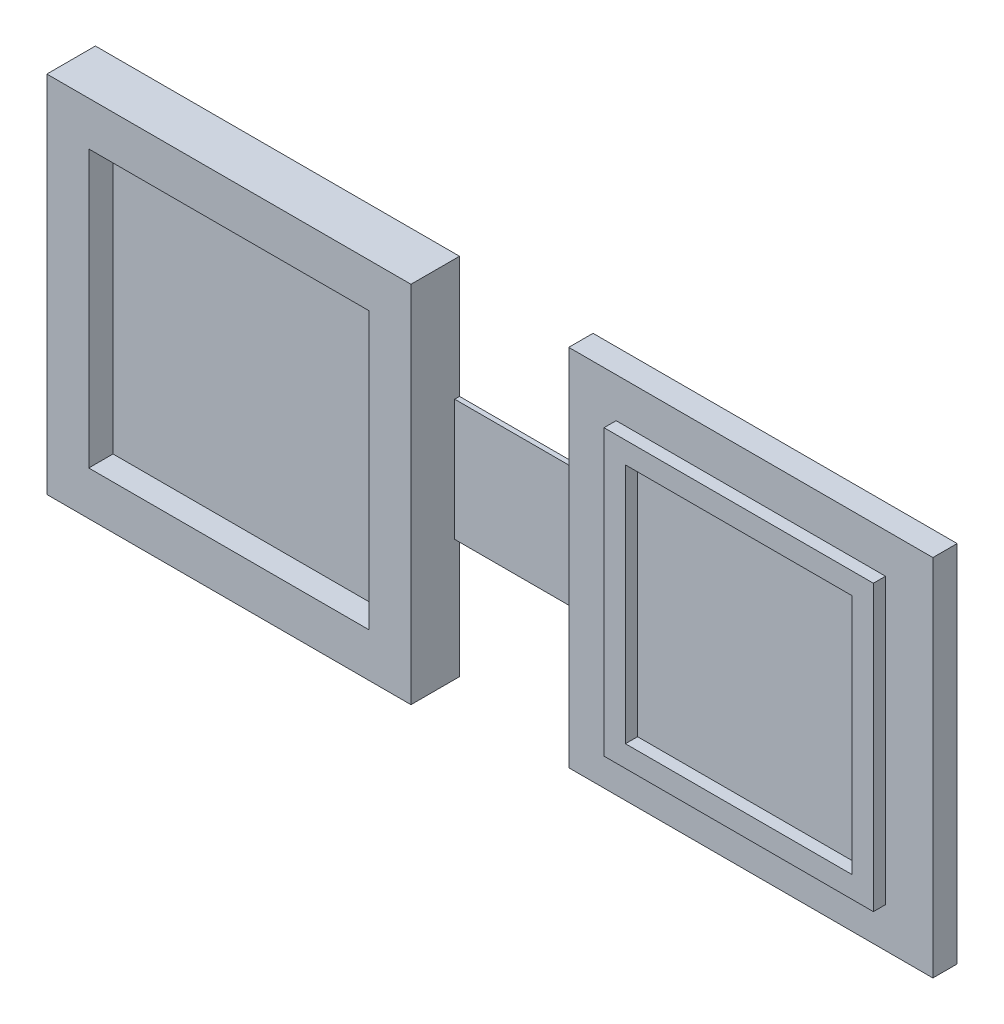
SolidWorks part; units mm, degrees
ref_plane "Front Plane" through (0, 0, 0) normal (0, 0, 1) x (1, 0, 0)
ref_plane "Top Plane" through (0, 0, 0) normal (0, 1, 0) x (1, 0, 0)
ref_plane "Right Plane" through (0, 0, 0) normal (1, 0, 0) x (0, 0, -1)
sketch "Sketch1" plane through (0, 0, 0) normal (0, 0, 1) x (1, 0, 0)
  line L0 (-28.8762, 21.913) -> (-28.8762, 11.913)
  line L1 (-58.8762, 21.913) -> (-28.8762, 21.913)
  line L2 (-58.8762, 21.913) -> (-58.8762, -8.087)
  line L3 (-58.8762, -8.087) -> (-28.8762, -8.087)
  line L5 (-28.8762, 11.913) -> (-28.8762, 1.913)
  line L6 (-28.8762, 1.913) -> (-28.8762, -8.087)
  line L7 (-28.8762, 11.913) -> (-17.8762, 11.913)
  line L8 (-17.8762, 11.913) -> (-17.8762, 21.913)
  line L9 (-17.8762, 21.913) -> (12.1238, 21.913)
  line L10 (12.1238, 21.913) -> (12.1238, -8.087)
  line L11 (12.1238, -8.087) -> (-17.8762, -8.087)
  line L12 (-17.8762, -8.087) -> (-17.8762, 1.913)
  line L13 (-17.8762, 1.913) -> (-17.8762, 11.913)
  line L14 (-17.8762, 1.913) -> (-28.8762, 1.913)
  line L15 (-55.4237, 18.2965) -> (-58.8762, 21.913)
  line L16 (-55.4237, 18.2965) -> (-32.3288, 18.2965)
  line L17 (-55.4237, 18.2965) -> (-55.4237, -4.4704)
  line L18 (-55.4237, -4.4704) -> (-32.3288, -4.4704)
  line L19 (-32.3288, 18.2965) -> (-32.3288, -4.4704)
  line L20 (-13.9734, 18.63) -> (8.2209, 18.63)
  line L21 (-13.9734, 18.63) -> (-13.9734, -4.804)
  line L22 (-13.9734, -4.804) -> (8.2209, -4.804)
  line L23 (8.2209, 18.63) -> (8.2209, -4.804)
  line L24 (-12.2057, 16.8623) -> (6.4532, 16.8623)
  line L25 (-12.2057, 16.8623) -> (-12.2057, -3.0362)
  line L26 (-12.2057, -3.0362) -> (6.4532, -3.0362)
  line L27 (6.4532, 16.8623) -> (6.4532, -3.0362)
  line L28 (-32.3288, 18.2965) -> (-28.8762, 21.913)
  line L29 (-32.3288, -4.4704) -> (-28.8762, -8.087)
  line L30 (-13.9734, 18.63) -> (-17.8762, 21.913)
  line L31 (8.2209, 18.63) -> (12.1238, 21.913)
  line L32 (8.2209, -4.804) -> (12.1238, -8.087)
  line L33 (-12.2057, 16.8623) -> (-13.9734, 18.63)
  line L34 (6.4532, 16.8623) -> (8.2209, 18.63)
  line L35 (6.4532, -3.0362) -> (8.2209, -4.804)
  line L36 (-12.2057, 16.8623) -> (-12.2057, 18.63)
  line L37 (-13.9734, 16.8623) -> (-12.2057, 16.8623)
  line L38 (8.2209, -3.0362) -> (6.4532, -3.0362)
  line L39 (6.4532, -4.804) -> (6.4532, -3.0362)
  dimension "D1" = 30
  dimension "D2" = 30
  dimension "D3" = 30
  dimension "D4" = 11
  dimension "D5" = 5
  dimension "D6" = 5
  dimension "D7" = 5
  dimension "D8" = 5.1
  dimension "D9" = 5.1
  dimension "D10" = 5.1
  dimension "D11" = 2.5
  dimension "D12" = 30
extrude "Boss-Extrude1" add sketch "Sketch1" along normal blind 2 contours L19 L16 L17 L18 | L27 L24 L25 L26 | L16 L28 L1 L15 | L29 L18 L17 L15 L2 L3 | L19 L29 L6 L5 L0 L28 | L32 L22 L21 L30 L8 L13 L12 L11 | L23 L32 L10 L31 | L20 L31 L9 L30 | L38 L23 L34 L27 | L36 L24 L34 L20 | L22 L39 L26 L25 L37 L21 | L21 L37 L33 | L33 L36 L20 | L39 L22 L35 | L23 L38 L35 region at (-43.8762, 20.1831, 0) region at (-30.5237, 6.913, 0) region at (-57.4568, 19.8118, 0) region at (-43.8762, 6.913, 0) region at (-17.452, 16.913, 0) region at (-2.8762, 20.3534, 0) region at (10.2523, 6.913, 0) region at (-13.3842, 17.4515, 0) region at (-12.7949, 18.0408, 0) region at (-2.4276, 17.7595, 0) region at (7.3496, 7.3613, 0) region at (-13.0896, 16.5645, 0) region at (-2.8762, 6.913, 0) region at (7.6317, -3.6254, 0) region at (7.0424, -4.2147, 0)
extrude "Boss-Extrude2" add sketch "Sketch1<3>" along normal blind 4 contours L19 L29 L6 L5 L0 L28 | L16 L28 L1 L15 | L29 L18 L17 L15 L2 L3 region at (-43.8762, 20.1831, 0) region at (-30.5237, 6.913, 0) region at (-57.4568, 19.8118, 0)
sketch "Sketch1<3>" plane through (0, 0, 0) normal (0, 0, 1) x (1, 0, 0) same geometry as "Sketch1"
extrude "Boss-Extrude3" add sketch "Sketch1<4>" along normal blind 3 contours L36 L24 L34 L20 | L33 L36 L20 | L21 L37 L33 | L22 L39 L26 L25 L37 L21 | L38 L23 L34 L27 | L23 L38 L35 | L39 L22 L35 region at (-13.3842, 17.4515, 0) region at (-12.7949, 18.0408, 0) region at (-2.4276, 17.7595, 0) region at (7.3496, 7.3613, 0) region at (-13.0896, 16.5645, 0) region at (7.6317, -3.6254, 0) region at (7.0424, -4.2147, 0)
sketch "Sketch1<4>" plane through (0, 0, 0) normal (0, 0, 1) x (1, 0, 0) same geometry as "Sketch1"
extrude "Boss-Extrude4" add sketch "Sketch1<5>" along normal blind 0.4 contours L14 L13 L7 L5 region at (-23.3762, 6.913, 0)
sketch "Sketch1<5>" plane through (0, 0, 0) normal (0, 0, 1) x (1, 0, 0) same geometry as "Sketch1"
